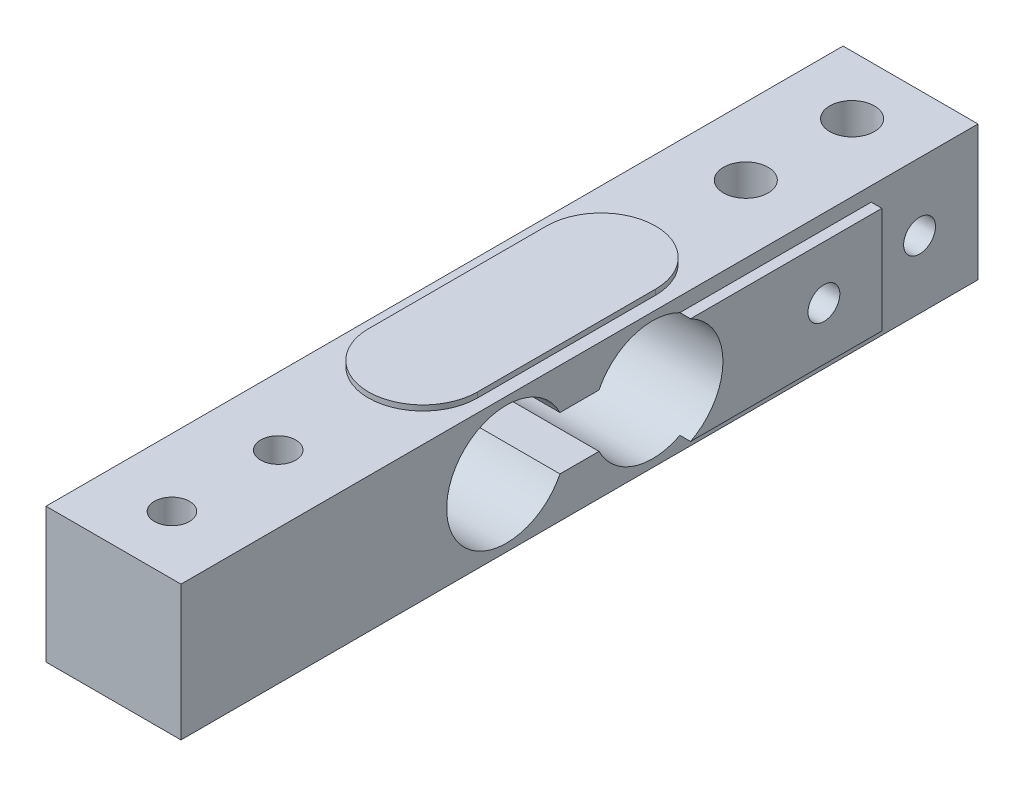
SolidWorks part; units mm, degrees
ref_plane "Front Plane" through (0, 0, 0) normal (0, 0, 1) x (1, 0, 0)
ref_plane "Top Plane" through (0, 0, 0) normal (0, 1, 0) x (1, 0, 0)
ref_plane "Right Plane" through (0, 0, 0) normal (1, 0, 0) x (0, 0, -1)
sketch "Sketch1" plane through (0, 0, 0) normal (1, 0, 0) x (0, 0, -1)
  line L1 (-37.5, -6.35) -> (37.5, -6.35)
  line L2 (-37.5, -6.35) -> (-37.5, 6.35)
  line L3 (-37.5, 6.35) -> (37.5, 6.35)
  line L4 (37.5, -6.35) -> (37.5, 6.35)
  line L5 (-37.5, -6.35) -> (37.5, 6.35) construction
  line L6 (-37.5, 6.35) -> (37.5, -6.35) construction
  point P0 (0, 0)
  dimension "D1" = 12.7
  dimension "D2" = 75
extrude "Boss-Extrude1" add sketch "Sketch1" along normal mid plane 12.7
sketch "Sketch2" plane through (0, 0, 0) normal (1, 0, 0) x (0, 0, -1)
  line L0 (-6.875, 0) -> (6.875, 0) construction
  line L1 (-12.5, 0) -> (12.5, 0) construction
  circle A0 centre (-6.875, 0) radius 5.625
  circle A1 centre (6.875, 0) radius 5.625
  point P4 (0, 0)
  dimension "D2" = 11.25
  dimension "D1" = 25
extrude "Cut-Extrude1" cut sketch "Sketch2" against normal through all both and the other way through all
sketch "Sketch3" plane through (0, 0, 0) normal (1, 0, 0) x (0, 0, -1)
  line L1 (-11.9139, -2.5) -> (11.9139, -2.5)
  line L2 (-11.9139, -2.5) -> (-11.9139, 2.5)
  line L3 (-11.9139, 2.5) -> (11.9139, 2.5)
  line L4 (11.9139, -2.5) -> (11.9139, 2.5)
  line L5 (-11.9139, -2.5) -> (11.9139, 2.5) construction
  line L6 (-11.9139, 2.5) -> (11.9139, -2.5) construction
  circle A0 centre (6.875, 0) radius 5.625 construction
  point P0 (0, 0)
  dimension "D1" = 5
extrude "Cut-Extrude2" cut sketch "Sketch3" against normal through all both and the other way through all
hole_wizard "M4x0.7 Tapped Hole1" positions "Sketch10" profile "Sketch5" tap size "M4x0.7" standard "ANSI Metric" end condition through all
sketch "Sketch10" plane through (0, 6.35, 0) normal (0, 1, 0) x (1, 0, 0)
  line L0 (0, 32) -> (0, 22) construction
  line L2 (0, 22) -> (0, -22) construction
  line L4 (0, -22) -> (0, -32) construction
  point P0 (0, 32)
  point P2 (0, 22)
  point P4 (0, -22)
  point P6 (0, -32)
  point P20 (0, 0)
  dimension "D1" = 44
  dimension "D2" = 10
cosmetic thread "Hole Thread1"
cosmetic thread "Hole Thread2"
cosmetic thread "Hole Thread3"
cosmetic thread "Hole Thread4"
sketch "Sketch5" plane through (0, 6.35, -32) normal (1, 0, 0) x (0, 0, 1)
  line L0 (0, 0) -> (0, 12.7)
  line L1 (0, 12.7) -> (1.65, 12.7)
  line L2 (1.65, 12.7) -> (1.65, 0)
  line L5 (1.65, 0) -> (0, 0)
  line L11 (0, -6.35) -> (0, 107.95) construction
  dimension "Thru Tap Drill Dia." = 3.3
  dimension "Thru Tap Drill Depth" = 12.7
sketch "Sketch8" plane through (0, 6.35, 0) normal (0, 1, 0) x (1, 0, 0)
  line L0 (0, -8.3778) -> (0, 8.3778) construction
  line L1 (-5.1373, -8.3778) -> (-5.1373, 8.3778)
  line L2 (5.1373, -8.3778) -> (5.1373, 8.3778)
  arc A0 (-5.1373, -8.3778) -> (5.1373, -8.3778) centre (0, -8.3778) ccw
  arc A1 (5.1373, 8.3778) -> (-5.1373, 8.3778) centre (0, 8.3778) ccw
  point P2 (0, 0)
extrude "Goo" add sketch "Sketch8" along normal mid plane 1
mirror "Mirror1" about plane through (0, 0, 0) normal (0, 1, 0) of "Goo"
ref_axis "Axis1" through (0, -6.35, -22) along (0, 1, 0)
ref_axis "Axis2" through (0, -6.35, -32) along (0, 1, 0)
sketch "Sketch9" plane through (6.35, 0, 0) normal (1, 0, 0) x (0, 0, -1)
  line L1 (9.4519, -5) -> (27.4519, -5)
  line L3 (9.4519, 5) -> (27.4519, 5)
  line L4 (27.4519, -5) -> (27.4519, 5)
  line L5 (9.4519, -5) -> (27.4519, 5) construction
  line L6 (9.4519, 5) -> (27.4519, -5) construction
  arc A0 (1.8361, -2.5) -> (1.8361, 2.5) centre (6.875, 0) ccw construction
  arc A1 (9.4519, -5) -> (9.4519, 5) centre (6.875, 0) ccw
  point P0 (18.4519, 0)
  point P5 (0, 0)
  point P9 (0, 0)
  point P11 (8.3165, 5.4372)
  point P12 (28.5366, -4.2701)
  point P13 (27.7335, 4.8445)
  dimension "D1" = 18
  dimension "D2" = 10
extrude "Boss-Extrude5" add sketch "Sketch9" along normal mid plane 2
hole_wizard "Ø3.0mm Dowel Hole1" positions "Sketch14" profile "Sketch12" hole size "Ø3.0" standard "ANSI Metric" end condition through all
sketch "Sketch14" plane through (-6.35, 0, 0) normal (-1, 0, 0) x (0, 0, 1)
  line L0 (-22, -6.35) -> (-22, 6.35) construction
  line L1 (-32, -6.35) -> (-32, 6.35) construction
  point P0 (-22, 0)
  point P2 (-32, 0)
  point P12 (-23.9334, 0)
  point P15 (0, 0)
  point P16 (0, 0)
sketch "Sketch12" plane through (-6.35, 0, -22) normal (0, 1, 0) x (0, 0, 1)
  line L0 (0, 0) -> (0, 13.7)
  line L1 (0, 13.7) -> (1.5, 13.7)
  line L2 (1.5, 13.7) -> (1.5, 0)
  line L5 (1.5, 0) -> (0, 0)
  line L11 (0, -6.35) -> (0, 107.95) construction
  dimension "Thru Hole Dia." = 3
  dimension "Thru Hole Depth" = 13.7
hole_wizard "M5x0.8 Tapped Hole1" positions "Sketch17" profile "Sketch16" tap size "M5x0.8" standard "ANSI Metric" end condition through all
sketch "Sketch17" plane through (0, 6.35, 0) normal (0, 1, 0) x (1, 0, 0)
  point P0 (0, 32)
  point P3 (0, 22)
sketch "Sketch16" plane through (0, 6.35, -32) normal (1, 0, 0) x (0, 0, 1)
  line L0 (0, 0) -> (0, 13.2)
  line L1 (0, 13.2) -> (2.1, 13.2)
  line L2 (2.1, 13.2) -> (2.1, 0)
  line L5 (2.1, 0) -> (0, 0)
  line L11 (0, -6.35) -> (0, 107.95) construction
  dimension "Thru Tap Drill Dia." = 4.2
  dimension "Thru Tap Drill Depth" = 13.2
cosmetic thread "Hole Thread5"
cosmetic thread "Hole Thread6"
